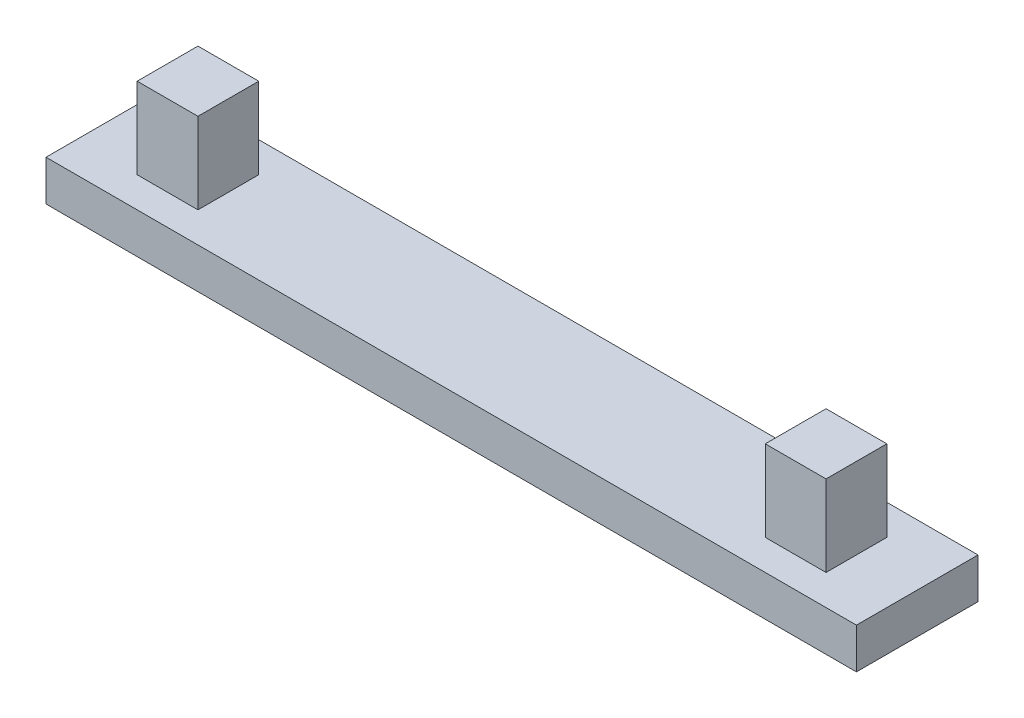
SolidWorks part; units mm, degrees
ref_plane "Front Plane" through (0, 0, 0) normal (0, 0, 1) x (1, 0, 0)
ref_plane "Top Plane" through (0, 0, 0) normal (0, 1, 0) x (1, 0, 0)
ref_plane "Right Plane" through (0, 0, 0) normal (1, 0, 0) x (0, 0, -1)
sketch "Sketch1" plane through (0, 0, 0) normal (0, 1, 0) x (1, 0, 0)
  line L1 (0, 0) -> (20, 0)
  line L2 (0, 0) -> (0, 3)
  line L3 (0, 3) -> (20, 3)
  line L4 (20, 0) -> (20, 3)
  line L5 (0, 0) -> (20, 3) construction
  line L6 (0, 3) -> (20, 0) construction
  line L7 (1.5, 2.25) -> (3, 2.25)
  line L8 (1.5, 2.25) -> (1.5, 0.75)
  line L9 (1.5, 0.75) -> (3, 0.75)
  line L10 (3, 2.25) -> (3, 0.75)
  line L11 (1.5, 2.25) -> (3, 0.75) construction
  line L12 (1.5, 0.75) -> (3, 2.25) construction
  line L13 (17, 2.25) -> (18.5, 2.25)
  line L14 (17, 2.25) -> (17, 0.75)
  line L15 (17, 0.75) -> (18.5, 0.75)
  line L16 (18.5, 2.25) -> (18.5, 0.75)
  line L17 (17, 2.25) -> (18.5, 0.75) construction
  line L18 (17, 0.75) -> (18.5, 2.25) construction
  point P4 (10, 1.5)
  point P10 (2.25, 1.5)
  point P15 (17.75, 1.5)
  point P16 (0, 0)
  point P17 (0, 1.5)
  point P18 (0, 0)
  point P19 (0, 0)
  point P20 (0, 0)
  point P21 (0, 0)
  point P22 (20, 1.5)
  dimension "D1" = 20
  dimension "D2" = 3
  dimension "D3" = 15.5
  dimension "D4" = 1.5
  dimension "D5" = 7.75
extrude "Boss-Extrude1" add sketch "Sketch1" along normal blind 1 contours L1 L4 L3 L2 L7 L10 L9 L8 L13 L16 L15 L14 region at (10, 0, -1.5)
ref_plane "Plane1" through (3, 0, -2.25) normal (1, 0, 0) x (0, 0, -1)
extrude "Boss-Extrude2" add sketch "Sketch1<3>" along normal blind 3 contours L7 L10 L9 L8 | L13 L16 L15 L14
sketch "Sketch1<3>" plane through (0, 0, 0) normal (0, 1, 0) x (1, 0, 0) same geometry as "Sketch1"
